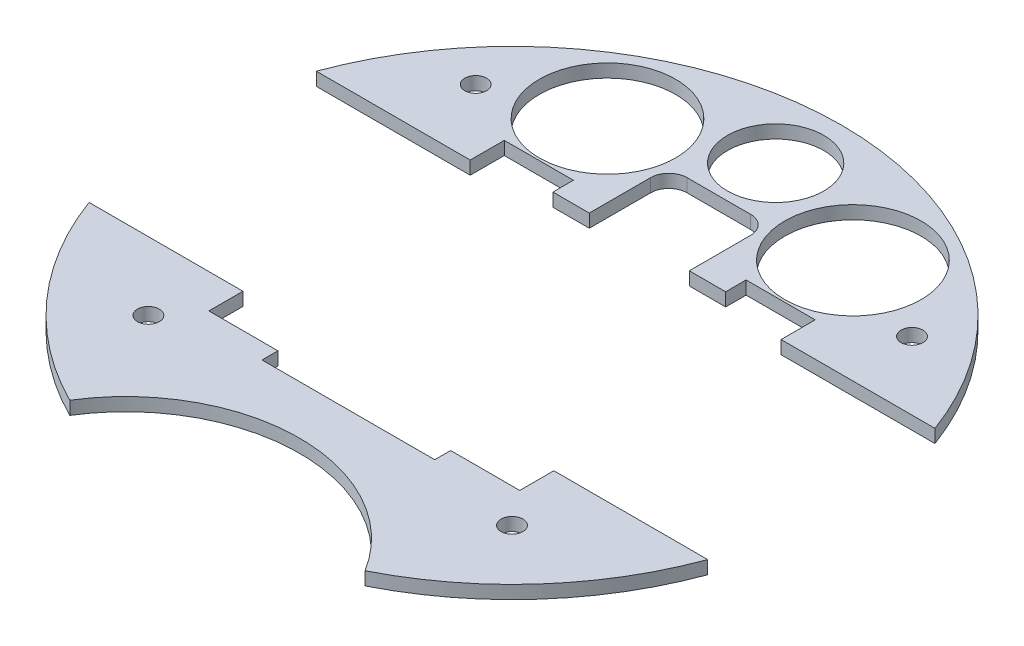
SolidWorks part; units mm, degrees
material "ABS"
ref_plane "Front Plane" through (0, 0, 0) normal (0, 0, 1) x (1, 0, 0)
ref_plane "Top Plane" through (0, 0, 0) normal (0, 1, 0) x (1, 0, 0)
ref_plane "Right Plane" through (0, 0, 0) normal (1, 0, 0) x (0, 0, -1)
sketch "Sketch1" plane through (0, 0, 0) normal (0, 1, 0) x (1, 0, 0)
  line L0 (0, -85) -> (-32.4891, -64.8129) construction
  line L1 (0, -85) -> (0, 0) construction
  arc A0 (32.4891, -64.8129) -> (-32.4891, -64.8129) centre (0, 0) ccw
  arc A1 (32.4891, -64.8129) -> (-32.4891, -64.8129) centre (0, -85) ccw
  dimension "D1" = 145
  dimension "D2" = 76.5
  dimension "D3" = 85
extrude "Boss-Extrude1" add sketch "Sketch1" along normal blind 2.9
sketch "solenoid placement" plane through (0, 2.9, 0) normal (0, 1, 0) x (1, 0, 0)
  line L4 (-19, -36) -> (19, -36)
  line L5 (-19, -36) -> (19, -36)
  line L6 (19, -36) -> (19, 28)
  line L7 (19, -36) -> (19, 28)
  line L8 (19, 28) -> (-19, 28)
  line L9 (19, 28) -> (-19, 28)
  line L10 (-19, 28) -> (-19, -36)
  line L11 (-19, 28) -> (-19, -36)
  circle A1 centre (0, 0) radius 72.5 construction
  arc A2 (32.4891, -64.8129) -> (-32.4891, -64.8129) centre (0, 0) ccw construction
  dimension "D1" = 0
extrude "Cut-Extrude1" cut sketch "solenoid placement" against normal through all
sketch "Sketch3" plane through (0, 2.9, 0) normal (0, 1, 0) x (1, 0, 0)
  circle A1 centre (27, 48) radius 12
  circle A2 centre (-27, 48) radius 12
  dimension "D1" = 24
extrude "Cut-Extrude3" cut sketch "Sketch3" against normal through all
sketch "Sketch4" plane through (0, 2.9, 0) normal (0, 1, 0) x (1, 0, 0)
  circle A2 centre (40, -40) radius 2.4
  circle A3 centre (40, -40) radius 2.4
  circle A4 centre (-40, -40) radius 2.4
  circle A5 centre (-40, -40) radius 2.4
  circle A6 centre (48, 40) radius 2.4
  circle A7 centre (48, 40) radius 2.4
  circle A8 centre (-48, 40) radius 2.4
  circle A12 centre (-48, 40) radius 2.4
  dimension "D1" = 0
  dimension "D2" = 0
  dimension "D3" = 0
  dimension "D4" = 0
extrude "Cut-Extrude4" cut sketch "Sketch4" against normal through all
sketch "Sketch2" plane through (0, 2.9, 0) normal (0, 1, 0) x (1, 0, 0)
  line L9 (-34.2, -32.5) -> (-22.2, -32.5)
  line L10 (-22.2, -32.5) -> (-19, -32.5)
  line L11 (-19, -32.5) -> (-19, 32.5)
  line L12 (-19, 32.5) -> (-22.2, 32.5)
  line L13 (-22.2, 32.5) -> (-34.2, 32.5)
  line L14 (-34.2, 32.5) -> (-34.2, 25)
  line L15 (-34.2, 25) -> (-68.0533, 25)
  line L16 (-68.0533, -25) -> (-34.2, -25)
  line L17 (-34.2, -25) -> (-34.2, -32.5)
  line L18 (-34.2, -32.5) -> (-22.2, -32.5)
  line L19 (-22.2, -32.5) -> (-19, -32.5)
  line L20 (-19, -32.5) -> (-19, 32.5)
  line L21 (-19, 32.5) -> (-22.2, 32.5)
  line L22 (-22.2, 32.5) -> (-34.2, 32.5)
  line L23 (-34.2, 32.5) -> (-34.2, 25)
  line L24 (-34.2, 25) -> (-68.0533, 25)
  line L25 (-68.0533, -25) -> (-34.2, -25)
  line L26 (-34.2, -25) -> (-34.2, -32.5)
  line L27 (19, 32.5) -> (19, -32.5)
  line L28 (19, -32.5) -> (22.2, -32.5)
  line L29 (22.2, -32.5) -> (34.2, -32.5)
  line L30 (34.2, -32.5) -> (34.2, -25)
  line L31 (34.2, -25) -> (68.0533, -25)
  line L32 (68.0533, 25) -> (34.2, 25)
  line L33 (34.2, 25) -> (34.2, 32.5)
  line L34 (34.2, 32.5) -> (22.2, 32.5)
  line L35 (22.2, 32.5) -> (19, 32.5)
  line L36 (19, 32.5) -> (19, -32.5)
  line L37 (19, -32.5) -> (22.2, -32.5)
  line L38 (22.2, -32.5) -> (34.2, -32.5)
  line L39 (34.2, -32.5) -> (34.2, -25)
  line L40 (34.2, -25) -> (68.0533, -25)
  line L41 (68.0533, 25) -> (34.2, 25)
  line L42 (34.2, 25) -> (34.2, 32.5)
  line L43 (34.2, 32.5) -> (22.2, 32.5)
  line L44 (22.2, 32.5) -> (19, 32.5)
  arc A2 (-68.0533, 25) -> (-68.0533, -25) centre (0, 0) ccw
  arc A3 (-68.0533, 25) -> (-68.0533, -25) centre (0, 0) ccw
  arc A4 (68.0533, -25) -> (68.0533, 25) centre (0, 0) ccw
  arc A5 (68.0533, -25) -> (68.0533, 25) centre (0, 0) ccw
  dimension "D2" = 0
  dimension "D1" = 0
extrude "Cut-Extrude2" cut sketch "Sketch2" against normal through all
sketch "Sketch5" plane through (0, 2.9, 0) normal (0, 1, 0) x (1, 0, 0)
  line L8 (-11, 28) -> (11, 28)
  line L9 (11, 28) -> (11, 41.5)
  line L10 (7, 45.5) -> (-7, 45.5)
  line L11 (-11, 41.5) -> (-11, 28)
  line L12 (19, 28) -> (-19, 28) construction
  arc A4 (11, 41.5) -> (7, 45.5) centre (7, 41.5) ccw
  arc A5 (-7, 45.5) -> (-11, 41.5) centre (-7, 41.5) ccw
  point P2 (0, 0)
  point P4 (0, 0)
  point P10 (0, 28)
  point P13 (0, 28)
  line M18 (-19, 28) -> (19, 28)
  dimension "D3" = 4
  dimension "D1" = 22
  dimension "D2" = 17.5
extrude "Cut-Extrude5" cut sketch "Sketch5" against normal through all contours L10 A5 L11 L9 A4 M18 region at (0, 2.9, -36.6073)
sketch "Sketch6" plane through (0, 2.9, 0) normal (0, 1, 0) x (-1, 0, 0)
  circle A1 centre (-27, -48) radius 15
  circle A2 centre (-27, -48) radius 15
  circle A3 centre (27, -48) radius 15
  circle A4 centre (27, -48) radius 15
  dimension "D1" = 0
  dimension "D2" = 0
extrude "Cut-Extrude10" cut sketch "Sketch6" against normal through all
sketch "Sketch7" plane through (0, 2.9, 0) normal (0, 1, 0) x (1, 0, 0)
  circle A1 centre (0, 58) radius 10.605
  circle A2 centre (0, 58) radius 10.605
  dimension "D1" = 0
extrude "Cut-Extrude11" cut sketch "Sketch7" against normal through all
equation "\"smallPulleyTeeth\"= 15"
equation "\"largePulleyTeeth\"= 30"
equation "\"eighthThick\"= 2.9mm"
equation "\"sixteenthThick\" = 1.7mm"
equation "\"quarterThick\"=6.0mm"
equation "\"OD\" = 145mm"
equation "\"puckAngle\" = 60.5deg"
equation "\"D1@Sketch1\"=\"OD\""
equation "\"puckDiam\" = 76.5mm"
equation "\"D2@Sketch1\"=\"puckDiam\""
equation "\"D1@Boss-Extrude1\"=\"eighthThick\""
equation "\"axlePress\" = 5.9mm"
equation "\"press\" = 0.2mm"
equation "\"wheelClear\" = 0.3mm"
equation "\"10-32clear\" = 4.8mm"
equation "\"6-32clear\" = 3.3mm"
equation "\"8-32clear\" = 4.0mm"
equation "\"wheelHeight\" = 22mm"
equation "\"wheelWell\" = 65mm"
equation "\"puckDist\" = 85mm"
equation "\"scoopFillet\" = 5mm"
equation "\"4-40clear\" = 3.0mm"
equation "\"D3@Sketch1\"=\"puckDist\""
